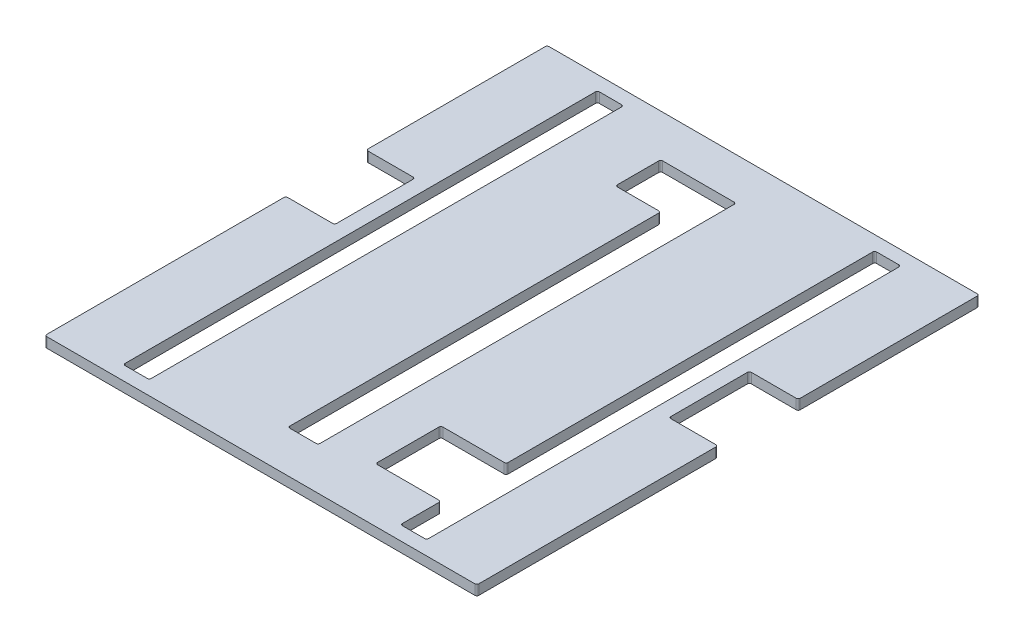
SolidWorks part; units mm, degrees
ref_plane "Front Plane" through (0, 0, 0) normal (0, 0, 1) x (1, 0, 0)
ref_plane "Top Plane" through (0, 0, 0) normal (0, 1, 0) x (1, 0, 0)
ref_plane "Right Plane" through (0, 0, 0) normal (1, 0, 0) x (0, 0, -1)
sketch "Sketch1" plane through (0, 0, 0) normal (0, 1, 0) x (1, 0, 0)
  line L1 (5911.0841, -8452.3124) -> (6341.0841, -8452.3124)
  line L2 (5911.0841, -8452.3124) -> (5911.0841, -8952.3124)
  line L3 (5911.0841, -8952.3124) -> (6341.0841, -8952.3124)
  line L4 (6341.0841, -8452.3124) -> (6341.0841, -8952.3124)
  dimension "D1" = 500
  dimension "D2" = 430
extrude "Boss-Extrude1" add sketch "Sketch1" along normal blind 10
sketch "Sketch2" plane through (0, 10, 0) normal (0, 1, 0) x (1, 0, 0)
  line L0 (5911.0841, -8452.3124) -> (5911.0841, -8952.3124) construction
  line L1 (5959.6841, -8712.448) -> (5911.0841, -8712.448)
  line L2 (5959.6841, -8712.448) -> (5959.6841, -8632.448)
  line L3 (5959.6841, -8632.448) -> (5911.0841, -8632.448)
  line L4 (5911.0841, -8712.448) -> (5911.0841, -8632.448)
  line L9 (6341.0841, -8952.3124) -> (6341.0841, -8452.3124) construction
  line L10 (6341.0841, -8712.448) -> (6292.4841, -8712.448)
  line L11 (6341.0841, -8712.448) -> (6341.0841, -8632.448)
  line L12 (6341.0841, -8632.448) -> (6292.4841, -8632.448)
  line L13 (6292.4841, -8712.448) -> (6292.4841, -8632.448)
  dimension "D1" = 48.6
  dimension "D2" = 80
  dimension "D3" = 80
  dimension "D4" = 48.6
extrude "Cut-Extrude1" cut sketch "Sketch2" against normal blind 10
sketch "Sketch3" plane through (0, 10, 0) normal (0, 1, 0) x (1, 0, 0)
  line L0 (5975.0841, -8541.6519) -> (5975.0841, -8938.3124)
  line L1 (6277.0841, -8938.3124) -> (6251.0841, -8938.3124)
  line L2 (6277.0841, -8938.3124) -> (6277.0841, -8466.3124)
  line L3 (6277.0841, -8466.3124) -> (6251.0841, -8466.3124)
  line L4 (6251.0841, -8938.3124) -> (6251.0841, -8466.3124)
  line L5 (5975.0841, -8466.3124) -> (6001.0841, -8466.3124)
  line L11 (5975.0841, -8938.3124) -> (6001.0841, -8938.3124)
  line L12 (6001.0841, -8466.3124) -> (6001.0841, -8938.3124)
  line L36 (5911.0841, -8712.448) -> (5911.0841, -8952.3124) construction
  line L37 (6341.0841, -8952.3124) -> (6341.0841, -8712.448) construction
  line L39 (6111.0841, -8494.3124) -> (6141.0841, -8494.3124)
  line L40 (6111.0841, -8539.3124) -> (6111.0841, -8910.3124)
  line L41 (6111.0841, -8910.3124) -> (6141.0841, -8910.3124)
  line L42 (6141.0841, -8494.3124) -> (6141.0841, -8910.3124)
  line L44 (6341.0841, -8452.3124) -> (5911.0841, -8452.3124) construction
  line L45 (5975.0841, -8466.3124) -> (5975.0841, -8541.6519)
  line L47 (5911.0841, -8952.3124) -> (6341.0841, -8952.3124) construction
  line L48 (6111.0841, -8494.3124) -> (6066.0841, -8494.3124)
  line L50 (6111.0841, -8539.3124) -> (6066.0841, -8539.3124)
  line L51 (6066.0841, -8494.3124) -> (6066.0841, -8539.3124)
  point P32 (6126.0841, -8452.3124)
  point P33 (6126.0841, -8494.3124)
  dimension "D15" = 42
  dimension "D22" = 45
  dimension "D1" = 26
  dimension "D2" = 472
  dimension "D3" = 26
  dimension "D4" = 472
  dimension "D6" = 64
  dimension "D7" = 45
  dimension "D8" = 64
  dimension "D10" = 416
  dimension "D11" = 110
  dimension "D20" = 14
  dimension "D21" = 14
extrude "Cut-Extrude2" cut sketch "Sketch3" against normal blind 10
sketch "Sketch4" plane through (0, 10, 0) normal (0, 1, 0) x (1, 0, 0)
  line L0 (6251.0841, -8466.3124) -> (6251.0841, -8938.3124) construction
  line L1 (6251.0841, -8898.0965) -> (6186.0841, -8898.0965)
  line L2 (6251.0841, -8898.0965) -> (6251.0841, -8833.0965)
  line L3 (6251.0841, -8833.0965) -> (6186.0841, -8833.0965)
  line L4 (6186.0841, -8898.0965) -> (6186.0841, -8833.0965)
  dimension "D1" = 65
  dimension "D2" = 65
extrude "Cut-Extrude3" cut sketch "Sketch4" against normal blind 10
fillet "Fillet2" radius 2 12 edges at (6292.4841, 5, 8632.448) (6341.0841, 5, 8632.448) (6341.0841, 5, 8712.448) (6292.4841, 5, 8712.448) (5959.6841, 5, 8632.448) (5959.6841, 5, 8712.448) (5911.0841, 5, 8712.448) (5911.0841, 5, 8632.448) (5911.0841, 5, 8452.3124) (6341.0841, 5, 8452.3124) (6341.0841, 5, 8952.3124) (5911.0841, 5, 8952.3124)
fillet "Fillet3" radius 2 18 edges at (6001.0841, 5, 8938.3124) (5975.0841, 5, 8938.3124) (6001.0841, 5, 8466.3124) (5975.0841, 5, 8466.3124) (6277.0841, 5, 8938.3124) (6251.0841, 5, 8938.3124) (6277.0841, 5, 8466.3124) (6251.0841, 5, 8466.3124) (6141.0841, 5, 8910.3124) (6111.0841, 5, 8910.3124) (6141.0841, 5, 8494.3124) (6111.0841, 5, 8539.3124) (6066.0841, 5, 8494.3124) (6066.0841, 5, 8539.3124) (6251.0841, 5, 8898.0965) (6251.0841, 5, 8833.0965) (6186.0841, 5, 8833.0965) (6186.0841, 5, 8898.0965)
